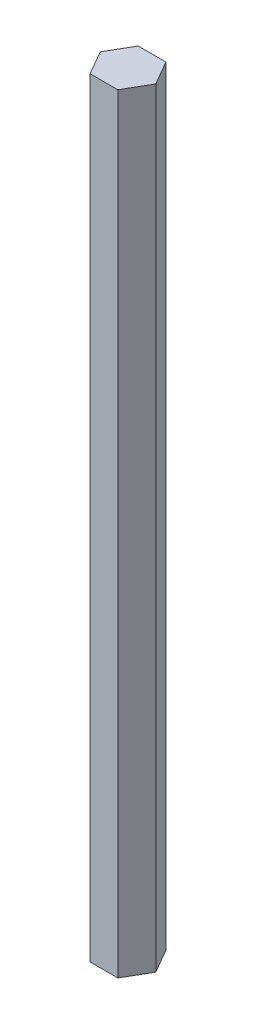
SolidWorks part; units mm, degrees
ref_plane "Front Plane" through (0, 0, 0) normal (0, 0, 1) x (1, 0, 0)
ref_plane "Top Plane" through (0, 0, 0) normal (0, 1, 0) x (1, 0, 0)
ref_plane "Right Plane" through (0, 0, 0) normal (1, 0, 0) x (0, 0, -1)
sketch "Sketch1" plane through (0, 0, 0) normal (0, 1, 0) x (1, 0, 0)
  line L9 (7.3323, 0) -> (3.6662, 6.35)
  line L10 (3.6662, 6.35) -> (-3.6662, 6.35)
  line L11 (-3.6662, 6.35) -> (-7.3323, 0)
  line L12 (-7.3323, 0) -> (-3.6662, -6.35)
  line L13 (-3.6662, -6.35) -> (3.6662, -6.35)
  line L14 (3.6662, -6.35) -> (7.3323, 0)
  circle A0 centre (0, 0) radius 6.35 construction
  dimension "D1" = 12.7
extrude "Boss-Extrude1" add sketch "Sketch1" along normal blind 203.2
